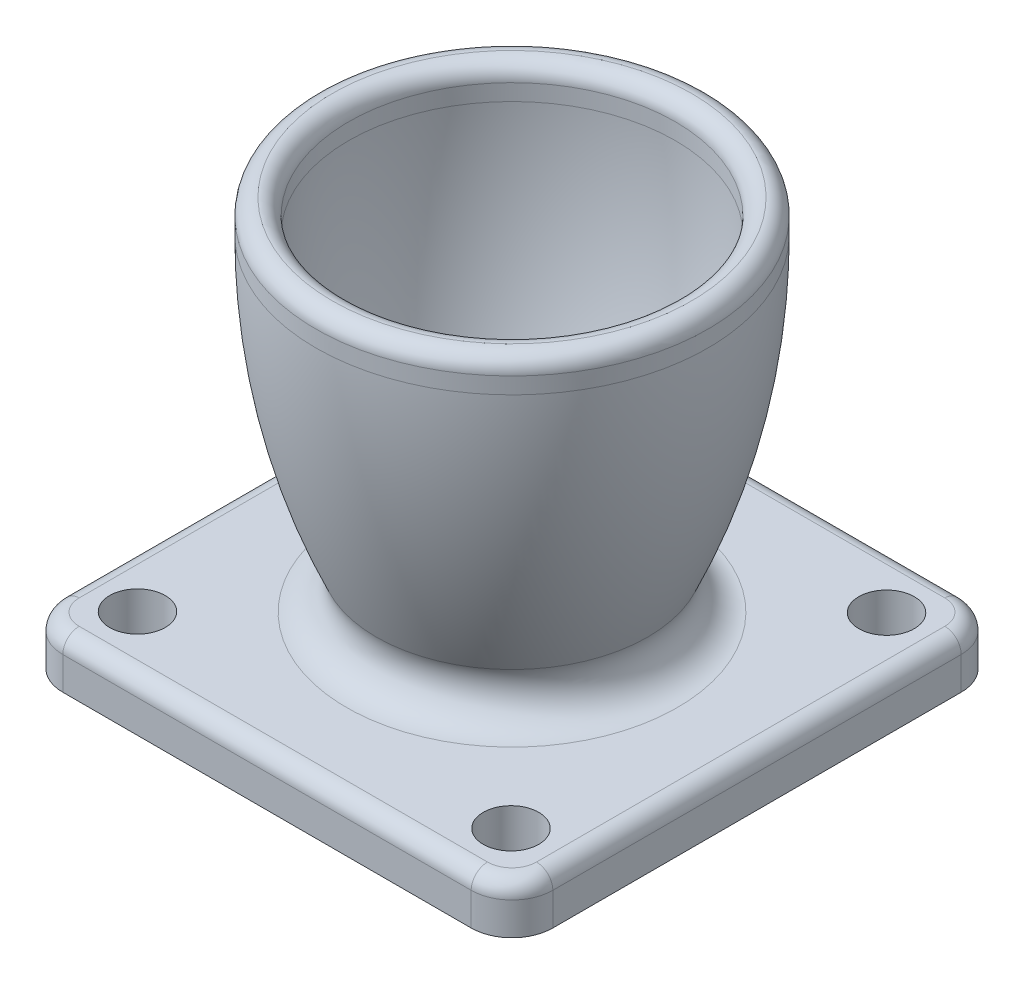
SolidWorks part; units mm, degrees
ref_plane "Front Plane" through (0, 0, 0) normal (0, 0, 1) x (1, 0, 0)
ref_plane "Top Plane" through (0, 0, 0) normal (0, 1, 0) x (1, 0, 0)
ref_plane "Right Plane" through (0, 0, 0) normal (1, 0, 0) x (0, 0, -1)
ref_axis "Axis1" through (0, 55, 0) along (0, -1, 0)
sketch "Sketch1" plane through (0, 0, 0) normal (0, 0, 1) x (1, 0, 0)
  line L0 (-4, 0) -> (-4, 2)
  line L1 (0, 0) -> (0, 30.4776) construction
  line L2 (0, 55) -> (0, -55) construction
  line L3 (-10, 23) -> (-10, 25)
  line L4 (-6, 0) -> (-6, 1.4361)
  line L5 (-12, 23) -> (-12, 25)
  line L6 (-12, 25) -> (-10, 25)
  line L7 (-6, 0) -> (-4, 0)
  arc A0 (-4, 2) -> (-10, 23) centre (29.75, 23) cw
  arc A1 (-6, 1.4361) -> (-12, 23) centre (29.75, 23) cw
  dimension "D1" = 8
  dimension "D2" = 2
  dimension "D3" = 2
  dimension "D4" = 20
  dimension "D5" = 25
  dimension "D6" = 2
revolve "Revolve1" add sketch "Sketch1" angle 360 about L1
sketch "Sketch2" plane through (0, 0, 0) normal (0, 1, 0) x (1, 0, 0)
  line L1 (-15, -15) -> (15, -15)
  line L2 (-15, -15) -> (-15, 15)
  line L3 (-15, 15) -> (15, 15)
  line L4 (15, -15) -> (15, 15)
  line L5 (-15, -15) -> (15, 15) construction
  line L6 (-15, 15) -> (15, -15) construction
  circle A2 centre (0, 0) radius 6 construction
  circle A3 centre (0, 0) radius 6
  point P0 (0, 0)
  dimension "D1" = 30
  dimension "D2" = 30
extrude "Boss-Extrude1" add sketch "Sketch2" along normal blind 3
hole_wizard "M3 Clearance Hole1" positions "Sketch3" profile "Sketch4" hole size "M3" standard "ANSI Metric" end condition through all
sketch "Sketch3" plane through (0, 3, 0) normal (0, 1, 0) x (1, 0, 0)
  line L0 (-11.4337, 11.4955) -> (11.4337, -11.4955) construction
  line L2 (-11.4955, -11.4337) -> (11.4955, 11.4337) construction
  point P0 (-11.4337, 11.4955)
  point P2 (11.4955, 11.4337)
  point P4 (11.4337, -11.4955)
  point P6 (-11.4955, -11.4337)
  dimension "D1" = 5
sketch "Sketch4" plane through (-11.4337, 3, -11.4955) normal (1, 0, 0) x (0, 0, 1)
  line L0 (0, 0) -> (0, 3)
  line L1 (0, 3) -> (1.7, 3)
  line L2 (1.7, 3) -> (1.7, 0)
  line L5 (1.7, 0) -> (0, 0)
  line L11 (0, -6.35) -> (0, 107.95) construction
  dimension "Thru Hole Dia." = 3.4
  dimension "Thru Hole Depth" = 3
fillet "Fillet1" radius 2.5 4 edges at (15, 1.5, -15) (-15, 1.5, -15) (-15, 1.5, 15) (15, 1.5, 15)
fillet "Fillet2" radius 2 1 edges at (0, 3, -6.8978)
fillet "Fillet3" radius 1 10 edges at (-14.2678, 3, 14.2678) (-15, 3, 0) (-14.2678, 3, -14.2678) (0, 3, -15) (14.2678, 3, -14.2678) (15, 3, 0) (14.2678, 3, 14.2678) (0, 3, 15) (0, 25, -10) (0, 25, -12)
fillet "Fillet4" radius 3 1 edges at (0, 2, -4)
